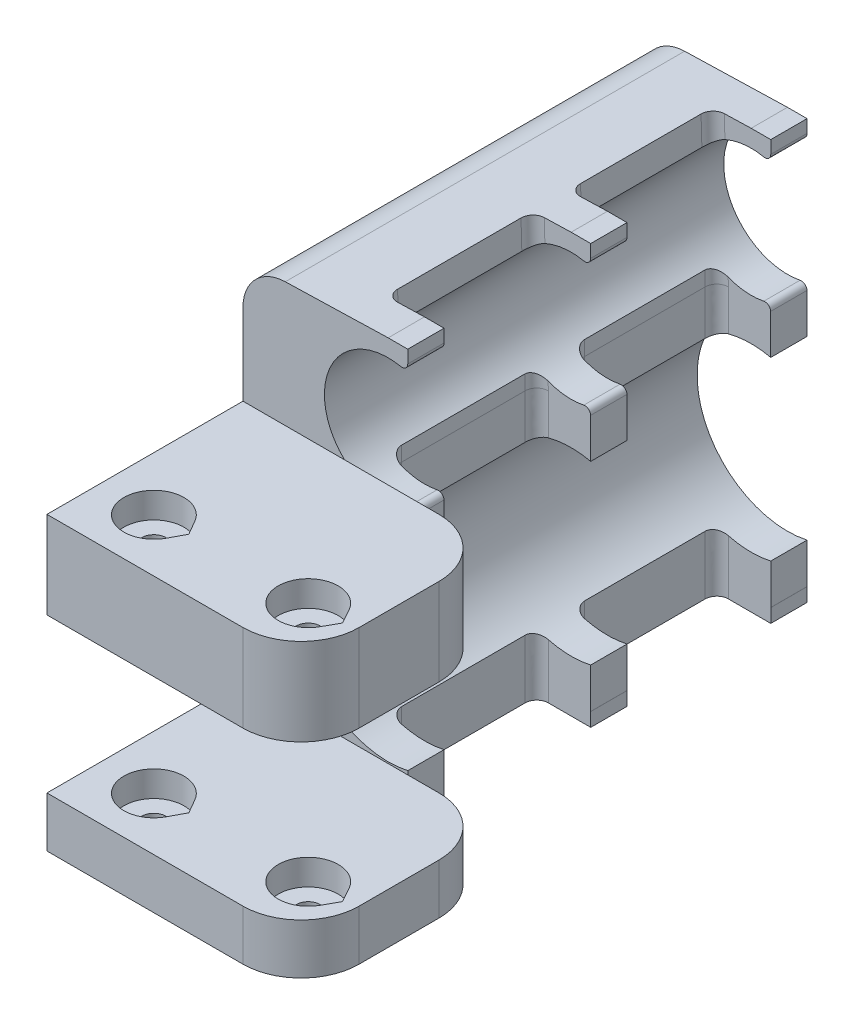
SolidWorks part; units mm, degrees
ref_plane "Front Plane" through (0, 0, 0) normal (0, 0, 1) x (1, 0, 0)
ref_plane "Top Plane" through (0, 0, 0) normal (0, 1, 0) x (1, 0, 0)
ref_plane "Right Plane" through (0, 0, 0) normal (1, 0, 0) x (0, 0, -1)
sketch "Sketch1" plane through (0, 0, 0) normal (0, 0, 1) x (1, 0, 0)
  line L0 (0, 0) -> (0, 13.2295) construction
  line L1 (3.429, -21.316) -> (3.429, -24.872)
  line L2 (0, -24.872) -> (-25.4, -24.872)
  line L3 (-25.4, 47.7241) -> (-25.4, -24.872)
  line L4 (3.429, 23.6544) -> (3.429, 21.316)
  line L5 (0, 48.4296) -> (-25.4, 47.7241)
  line L8 (0, 48.4296) -> (3.429, 48.4296)
  line L9 (3.429, 48.4296) -> (3.429, 44.8736)
  line L10 (3.429, -24.872) -> (0, -24.872)
  circle A0 centre (0, 0) radius 21.59 construction
  arc A1 (3.429, 21.316) -> (3.429, -21.316) centre (0, 0) ccw
  arc A2 (3.429, 44.8736) -> (3.429, 23.6544) centre (0, 34.264) ccw
  dimension "D1" = 22.3
  dimension "D2" = 3.556
  dimension "D3" = 3.556
  dimension "D4" = 3.429
  dimension "D5" = 25.4
extrude "Boss-Extrude1" add sketch "Sketch1" against normal blind 69.85
sketch "Sketch2" plane through (-1.3441, 48.3923, 0) normal (-0.0278, 0.9996, 0) x (0.9996, 0.0278, 0)
  line L0 (4.7723, 69.85) -> (4.7723, 0) construction
  line L1 (-5.3877, 63.5) -> (10.6572, 63.5)
  line L2 (-5.3877, 63.5) -> (-5.3877, 38.3544)
  line L3 (-5.3877, 38.3544) -> (10.6572, 38.3544)
  line L4 (10.6572, 63.5) -> (10.6572, 38.3544)
  line L5 (-5.3877, 32.0044) -> (10.6572, 32.0044)
  line L6 (-5.3877, 32.0044) -> (-5.3877, 6.35)
  line L7 (-5.3877, 6.35) -> (10.6572, 6.35)
  line L8 (10.6572, 32.0044) -> (10.6572, 6.35)
  line L9 (1.3446, 69.85) -> (-24.0652, 69.85) construction
  line L10 (1.3446, 0) -> (-24.0652, 0) construction
  dimension "D1" = 10.16
  dimension "D2" = 10.16
  dimension "D3" = 6.35
  dimension "D4" = 6.35
  dimension "D5" = 6.35
extrude "Cut-Extrude1" cut sketch "Sketch2" against normal through all and the other way blind 2.54
sketch "Sketch3" plane through (0, -24.872, 0) normal (0, -1, 0) x (1, 0, 0)
  line L0 (3.429, -32.0044) -> (-4.6989, -32.0044) construction
  line L1 (-4.6989, -6.35) -> (-14.8589, -6.35)
  line L3 (-7.6834, -32.0044) -> (-14.8589, -32.0044)
  line L4 (-14.8589, -6.35) -> (-14.8589, -32.0044)
  line L5 (-4.6989, -38.3544) -> (-14.8589, -38.3544)
  line L7 (-7.6834, -63.5) -> (-14.8589, -63.5)
  line L8 (-14.8589, -38.3544) -> (-14.8589, -63.5)
  line L9 (-4.6989, -6.35) -> (-4.3793, -6.35)
  line L11 (-7.6834, -32.0044) -> (-4.3793, -32.0044)
  line L12 (-4.3793, -6.35) -> (-4.3793, -32.0044)
  line L13 (3.429, -63.5) -> (-4.6989, -63.5) construction
  line L14 (-4.6989, -38.3544) -> (-2.4227, -38.3544)
  line L16 (-7.6834, -63.5) -> (-2.4227, -63.5)
  line L17 (-2.4227, -38.3544) -> (-2.4227, -63.5)
  dimension "D1" = 10.16
  dimension "D2" = 10.16
extrude "Cut-Extrude2" cut sketch "Sketch3" against normal blind 13.97
fillet "Fillet1" radius 1.016 12 edges at (3.429, 23.6544, -3.175) (3.429, -21.316, -3.175) (3.429, -21.316, -35.1794) (3.429, -21.316, -66.675) (3.429, 23.6544, -35.1794) (3.429, 23.6544, -66.675) (3.429, 44.8736, -3.175) (3.429, 44.8736, -35.1794) (3.429, 44.8736, -66.675) (3.429, 21.316, -66.675) (3.429, 21.316, -35.1794) (3.429, 21.316, -3.175)
fillet "Fillet2" radius 2.032 12 edges at (-6.6605, 45.75, -63.5) (-6.6605, 45.75, -32.0044) (-6.024, 22.834, -32.0044) (-6.024, 22.834, -63.5) (-14.8589, -20.2676, -63.5) (-14.8589, -20.2676, -38.3544) (-14.8589, -20.2676, -6.35) (-6.024, 22.834, -38.3544) (-6.6605, 45.75, -38.3544) (-6.6605, 45.75, -6.35) (-6.024, 22.834, -6.35) (-14.8589, -20.2676, -32.0044)
sketch "Sketch4" plane through (-25.4, 0, 0) normal (-1, 0, 0) x (0, 0, 1)
  line L0 (-69.85, 47.7241) -> (0, 47.7241) construction
  line L5 (0, 23.114) -> (0, 45.414) construction
  line L6 (0, 26.1341) -> (34.29, 26.1341)
  line L7 (0, 26.1341) -> (0, 10.8941)
  line L8 (0, 10.8941) -> (34.29, 10.8941)
  line L9 (34.29, 26.1341) -> (34.29, 10.8941)
  dimension "D1" = 15.24
  dimension "D2" = 21.59
  dimension "D3" = 34.29
extrude "Boss-Extrude2" add sketch "Sketch4" against normal blind 44.45
fillet "Fillet3" radius 10.16 2 edges at (19.05, 18.5141, 34.29) (19.05, 18.5141, 0)
sketch "Sketch5" plane through (0, 26.1341, 0) normal (0, 1, 0) x (1, 0, 0)
  line L0 (-25.4, -34.29) -> (-25.4, 0) construction
  line L1 (8.89, -34.29) -> (-25.4, -34.29) construction
  line L2 (13.91, -24.8934) -> (12.3807, -23.393)
  line L3 (13.91, -24.8934) -> (12.3793, -26.3924)
  line L4 (-12.98, -24.892) -> (-14.5659, -23.4475)
  line L5 (-12.98, -24.892) -> (-14.4579, -26.4468)
  arc A0 (12.3807, -23.393) -> (12.3793, -26.3924) centre (10.91, -24.892) ccw
  arc A1 (-14.5659, -23.4475) -> (-14.4579, -26.4468) centre (-15.98, -25) ccw
  point P0 (-15.98, -25)
  point P1 (10.91, -24.892)
  point P6 (13.91, -24.8934)
  point P11 (-12.98, -24.892)
  dimension "D5" = 4.2
  dimension "D1" = 26.89
  dimension "D2" = 9.42
  dimension "D3" = 9.29
  dimension "D4" = 9.398
  dimension "D6" = 3
  dimension "D7" = 3
extrude "Cut-Extrude3" cut sketch "Sketch5" against normal through all
fillet "Fillet4" radius 7.62 2 edges at (-25.4, -24.872, -34.925) (-25.4, 47.7241, -34.925)
sketch "Sketch6" plane through (0, 0, -69.85) normal (0, 0, -1) x (-1, 0, 0)
  line L0 (-3.429, -24.872) -> (-3.4285, -15.4235)
  line L1 (-3.4267, 22.4083) -> (25.4, 22.4083)
  line L2 (25.4, 40.3129) -> (25.4, -17.252) construction
  line L3 (25.4, 22.4083) -> (25.4, -24.872)
  line L4 (25.4, -24.872) -> (-3.429, -24.872)
  line L5 (-3.427, 15.4239) -> (-3.4267, 22.4083)
  arc A0 (-3.4285, -15.4235) -> (-3.427, 15.4239) centre (0, 0) ccw
  dimension "D1" = 31.6
extrude "Boss-Extrude3" add sketch "Sketch6" against normal blind 69.85
sketch "Sketch7" plane through (0, 22.4083, 0) normal (0, 1, 0) x (1, 0, 0)
  line L1 (3.4267, 32.0044) -> (-3.9794, 32.0044) construction
  line L2 (-6.0122, 29.9724) -> (-6.0122, 8.382) construction
  line L3 (-3.9794, 6.35) -> (3.4267, 6.35) construction
  line L5 (3.4267, 63.5) -> (-3.9794, 63.5) construction
  line L6 (-6.0122, 61.468) -> (-6.0122, 40.3864) construction
  line L7 (-3.9794, 38.3544) -> (3.4267, 38.3544) construction
  line L9 (3.4267, 32.0044) -> (-3.9794, 32.0044)
  line L10 (-6.0122, 29.9724) -> (-6.0122, 8.382)
  line L11 (-3.9794, 6.35) -> (3.4267, 6.35)
  line L13 (3.4267, 63.5) -> (-3.9794, 63.5)
  line L14 (-6.0122, 61.468) -> (-6.0122, 40.3864)
  line L15 (-3.9794, 38.3544) -> (3.4267, 38.3544)
  line L16 (3.4267, 63.5) -> (5.5294, 63.5)
  line L17 (5.5294, 63.5) -> (5.5294, 38.3544)
  line L18 (5.5294, 38.3544) -> (3.4267, 38.3544)
  line L19 (3.4267, 32.0044) -> (6.463, 32.0044)
  line L20 (6.463, 32.0044) -> (6.1335, 6.35)
  line L21 (6.1335, 6.35) -> (3.4267, 6.35)
  ellipse E0 centre (-3.9794, 29.9724) end of major axis (-6.0122, 29.9724) minor radius 2.032 (-3.9794, 32.0044) -> (-6.0122, 29.9724) ccw construction
  ellipse E1 centre (-3.9794, 8.382) end of major axis (-6.0122, 8.382) minor radius 2.032 (-6.0122, 8.382) -> (-3.9794, 6.35) ccw construction
  ellipse E2 centre (-3.9794, 61.468) end of major axis (-6.0122, 61.468) minor radius 2.032 (-3.9794, 63.5) -> (-6.0122, 61.468) ccw construction
  ellipse E3 centre (-3.9794, 40.3864) end of major axis (-6.0122, 40.3864) minor radius 2.032 (-6.0122, 40.3864) -> (-3.9794, 38.3544) ccw construction
  ellipse E4 centre (-3.9794, 29.9724) end of major axis (-6.0122, 29.9724) minor radius 2.032 (-3.9794, 32.0044) -> (-6.0122, 29.9724) ccw
  ellipse E5 centre (-3.9794, 8.382) end of major axis (-6.0122, 8.382) minor radius 2.032 (-6.0122, 8.382) -> (-3.9794, 6.35) ccw
  ellipse E6 centre (-3.9794, 61.468) end of major axis (-6.0122, 61.468) minor radius 2.032 (-3.9794, 63.5) -> (-6.0122, 61.468) ccw
  ellipse E7 centre (-3.9794, 40.3864) end of major axis (-6.0122, 40.3864) minor radius 2.032 (-6.0122, 40.3864) -> (-3.9794, 38.3544) ccw
extrude "Cut-Extrude4" cut sketch "Sketch7" against normal blind 69.85
sketch "Sketch9" plane through (0, 26.1341, 0) normal (0, 1, 0) x (1, 0, 0)
  line L0 (16.91, -24.892) -> (15.5038, -22.3504)
  line L1 (16.91, -24.892) -> (15.5038, -27.4336)
  line L2 (-9.981, -24.8897) -> (-11.4338, -22.3743)
  line L3 (-9.981, -24.8897) -> (-11.3403, -27.4567)
  arc A0 (15.5038, -22.3504) -> (15.5038, -27.4336) centre (10.91, -24.892) ccw
  arc A1 (-11.4338, -22.3743) -> (-11.3403, -27.4567) centre (-15.98, -25) ccw
  point P6 (16.91, -24.892)
  point P7 (-9.981, -24.8897)
  dimension "D1" = 10.5
  dimension "D2" = 6
  dimension "D3" = 6
extrude "Cut-Extrude5" cut sketch "Sketch9" against normal blind 4.5
sketch "Sketch10" plane through (0, 10.8941, 0) normal (0, -1, 0) x (1, 0, 0)
  line L0 (-9.981, 24.8897) -> (-11.4338, 22.3743) construction
  line L1 (-11.3403, 27.4567) -> (-9.981, 24.8897) construction
  line L2 (15.5038, 27.4336) -> (16.91, 24.892) construction
  line L3 (16.91, 24.892) -> (15.5038, 22.3504) construction
  line L4 (-9.981, 24.8897) -> (-11.4338, 22.3743)
  line L5 (-11.3403, 27.4567) -> (-9.981, 24.8897)
  line L6 (15.5038, 27.4336) -> (16.91, 24.892)
  line L7 (16.91, 24.892) -> (15.5038, 22.3504)
  arc A0 (-11.3403, 27.4567) -> (-11.4338, 22.3743) centre (-15.98, 25) ccw construction
  arc A1 (15.5038, 27.4336) -> (15.5038, 22.3504) centre (10.91, 24.892) ccw construction
  arc A2 (-11.3403, 27.4567) -> (-11.4338, 22.3743) centre (-15.98, 25) ccw
  arc A3 (15.5038, 27.4336) -> (15.5038, 22.3504) centre (10.91, 24.892) ccw
extrude "Cut-Extrude6" cut sketch "Sketch10" against normal blind 4.5
sketch "Sketch11" plane through (0, -24.872, 0) normal (0, -1, 0) x (1, 0, 0)
  line L1 (-14.4579, 26.4468) -> (-12.98, 24.892) construction
  line L2 (-12.98, 24.892) -> (-14.5659, 23.4475) construction
  line L3 (13.91, 24.8934) -> (12.3807, 23.393) construction
  line L4 (12.3793, 26.3924) -> (13.91, 24.8934) construction
  line L5 (19.05, 10.16) -> (19.05, 24.13)
  line L6 (8.89, 34.29) -> (-25.4, 34.29)
  line L7 (-25.4, 34.29) -> (-25.4, 0)
  line L8 (-25.4, 0) -> (-11.4437, 0)
  line L9 (-11.4437, 0) -> (8.89, 0)
  line L10 (19.05, 10.16) -> (19.05, 24.13)
  line L11 (8.89, 34.29) -> (-25.4, 34.29)
  line L12 (-25.4, 34.29) -> (-25.4, 0)
  line L13 (-25.4, 0) -> (-11.4437, 0)
  line L14 (-11.4437, 0) -> (8.89, 0)
  line L15 (-14.4579, 26.4468) -> (-12.98, 24.892)
  line L16 (-12.98, 24.892) -> (-14.5659, 23.4475)
  line L17 (13.91, 24.8934) -> (12.3807, 23.393)
  line L18 (12.3793, 26.3924) -> (13.91, 24.8934)
  arc A0 (-14.4579, 26.4468) -> (-14.5659, 23.4475) centre (-15.98, 25) ccw construction
  arc A1 (12.3793, 26.3924) -> (12.3807, 23.393) centre (10.91, 24.892) ccw construction
  arc A2 (19.05, 24.13) -> (8.89, 34.29) centre (8.89, 24.13) ccw
  arc A3 (8.89, 0) -> (19.05, 10.16) centre (8.89, 10.16) ccw
  arc A4 (19.05, 24.13) -> (8.89, 34.29) centre (8.89, 24.13) ccw
  arc A5 (8.89, 0) -> (19.05, 10.16) centre (8.89, 10.16) ccw
  arc A6 (-14.4579, 26.4468) -> (-14.5659, 23.4475) centre (-15.98, 25) ccw
  arc A7 (12.3793, 26.3924) -> (12.3807, 23.393) centre (10.91, 24.892) ccw
  dimension "D1" = 0
extrude "Boss-Extrude4" add sketch "Sketch11" against normal blind 8.8
sketch "Sketch12" plane through (0, -16.072, 0) normal (0, 1, 0) x (1, 0, 0)
  line L0 (-11.3403, -27.4567) -> (-9.981, -24.8897) construction
  line L1 (-9.981, -24.8897) -> (-11.4338, -22.3743) construction
  line L2 (16.91, -24.892) -> (15.5038, -22.3504) construction
  line L3 (15.5038, -27.4336) -> (16.91, -24.892) construction
  line L4 (-11.3403, -27.4567) -> (-9.981, -24.8897)
  line L5 (-9.981, -24.8897) -> (-11.4338, -22.3743)
  line L6 (16.91, -24.892) -> (15.5038, -22.3504)
  line L7 (15.5038, -27.4336) -> (16.91, -24.892)
  arc A0 (-11.4338, -22.3743) -> (-11.3403, -27.4567) centre (-15.98, -25) ccw construction
  arc A1 (15.5038, -22.3504) -> (15.5038, -27.4336) centre (10.91, -24.892) ccw construction
  arc A2 (-11.4338, -22.3743) -> (-11.3403, -27.4567) centre (-15.98, -25) ccw
  arc A3 (15.5038, -22.3504) -> (15.5038, -27.4336) centre (10.91, -24.892) ccw
extrude "Cut-Extrude7" cut sketch "Sketch12" against normal blind 4.5
